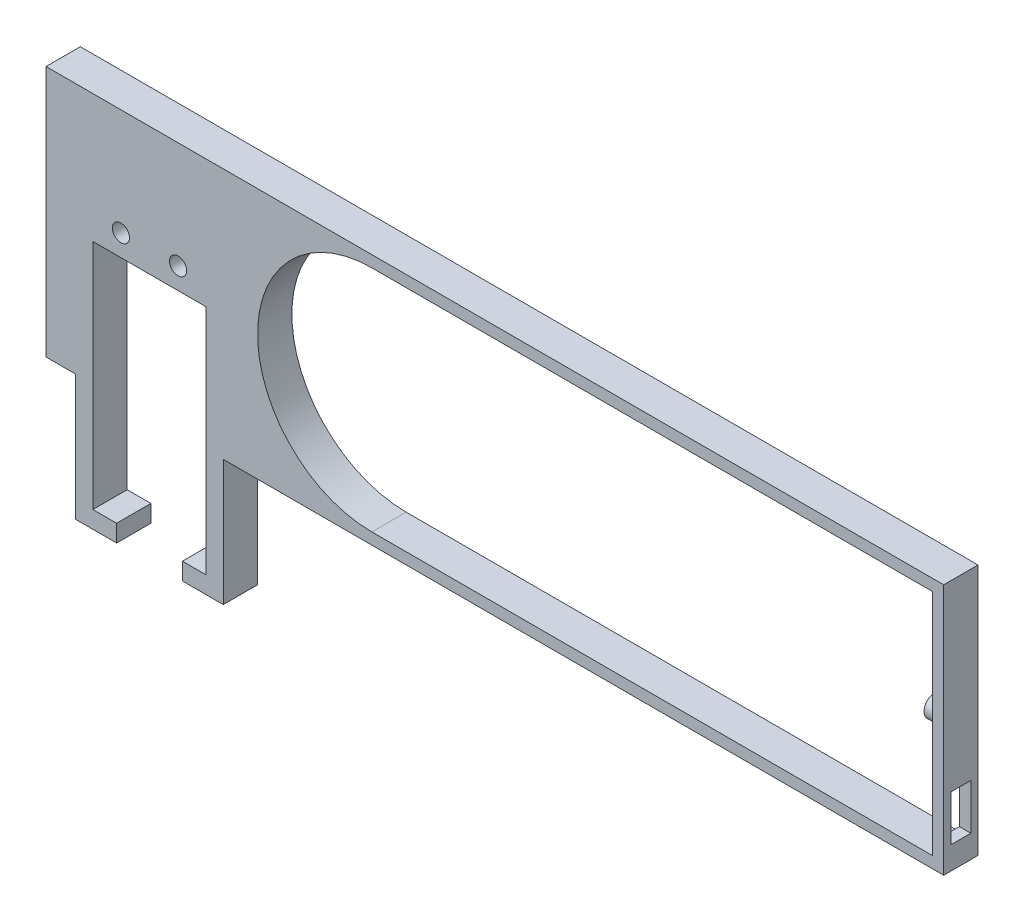
SolidWorks part; units mm, degrees
other "Markup1"
sketch "Sketch3" plane through (63.5, 44, 6) normal (0.035, 0.053, 0.998) x (0.9992, 0.0181, -0.036)
material "ABS"
ref_plane "Front Plane" through (0, 0, 0) normal (0, 0, 1) x (1, 0, 0)
ref_plane "Top Plane" through (0, 0, 0) normal (0, 1, 0) x (1, 0, 0)
ref_plane "Right Plane" through (0, 0, 0) normal (1, 0, 0) x (0, 0, -1)
sketch "Sketch1" plane through (0, 0, 0) normal (0, 0, 1) x (1, 0, 0)
  line L3 (0, 0) -> (100, 0)
  line L4 (100, 0) -> (100, 44)
  line L5 (100, 44) -> (0, 44)
  line L6 (0, 44) -> (-57, 44)
  line L7 (-57, 44) -> (-57, 0)
  line L8 (-57, 0) -> (-51.8, 0)
  line L9 (-51.8, 0) -> (-51.8, -22)
  line L10 (-51.8, -22) -> (-44.65, -22)
  line L11 (-44.65, -22) -> (-44.65, -19)
  line L12 (-44.65, -19) -> (-48.8, -19)
  line L13 (-48.8, -19) -> (-48.8, 21.6)
  line L14 (-48.8, 21.6) -> (-29, 21.6)
  line L15 (-29, 21.6) -> (-29, -19)
  line L16 (-29, -19) -> (-33.15, -19)
  line L17 (-33.15, -19) -> (-33.15, -22)
  line L18 (-33.15, -22) -> (-26, -22)
  line L20 (0, 2) -> (98, 2)
  line L21 (98, 2) -> (98, 42)
  line L22 (98, 42) -> (0, 42)
  line L23 (-43.9, 25.353) -> (-33.9, 25.353) construction
  line L24 (0, 0) -> (-26, 0)
  line L25 (-26, 0) -> (-26, -22)
  line L26 (-44.65, -19) -> (-33.15, -19) construction
  circle A1 centre (-43.9, 25.353) radius 1.5
  circle A2 centre (-33.9, 25.353) radius 1.5
  arc A3 (0, 42) -> (0, 2) centre (0, 22) ccw
  point P2 (-38.9, -19)
  point P28 (-38.9, 25.353)
  point P29 (-38.9, 21.6)
  point P30 (-20, 22)
  dimension "D1" = 2
  dimension "D5" = 20
  dimension "D7" = 3
  dimension "D8" = 3
  dimension "D2" = 2
  dimension "D3" = 2
  dimension "D4" = 120
  dimension "D6" = 3.753
  dimension "D9" = 10
  dimension "D10" = 8.2
  dimension "D11" = 40.6
  dimension "D12" = 19.8
  dimension "D13" = 11.5
  dimension "D14" = 3
  dimension "D15" = 3
  dimension "D16" = 3
  dimension "D17" = 22
  dimension "D18" = 37
extrude "Boss-Extrude1" add sketch "Sketch1" along normal blind 6
sketch "Sketch2" plane through (98, 0, 0) normal (-1, 0, 0) x (0, 0, 1)
  line L0 (3, 42) -> (3, 2) construction
  line L1 (6, 42) -> (0, 42) construction
  line L2 (6, 2) -> (0, 2) construction
  circle A0 centre (3, 22) radius 1.905
  point P2 (3, 22)
  dimension "D1" = 3.81
extrude "Boss-Extrude2" add sketch "Sketch2" along normal blind 2.54
sketch "Sketch4" plane through (98, 0, 0) normal (-1, 0, 0) x (0, 0, 1)
  line L0 (1.25, 12) -> (4.75, 12)
  line L1 (4.75, 12) -> (4.75, 4)
  line L2 (4.75, 4) -> (1.25, 4)
  line L3 (1.25, 4) -> (1.25, 12)
  line L4 (0, 2.4647) -> (6, 2.4647) construction
  line L5 (0, 2) -> (0, 42) construction
  line L6 (6, 2) -> (6, 42) construction
  line L7 (6, 2) -> (0, 2) construction
  point P10 (6, 2.4647)
  point P11 (3, 4)
  point P12 (3, 2.4647)
  dimension "D1" = 3.5
  dimension "D2" = 8
  dimension "D3" = 2
extrude "Cut-Extrude1" cut sketch "Sketch4" against normal up to surface (2 mm away) up to face at (100, 22, 3)
